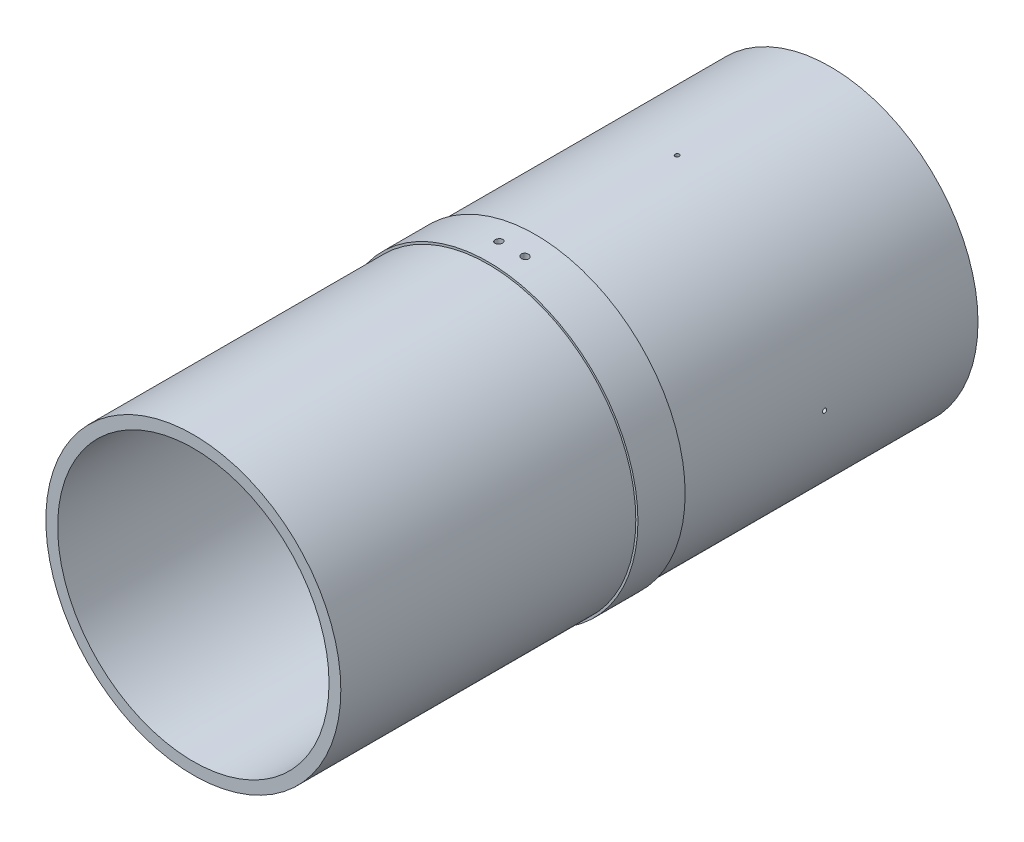
SolidWorks part; units mm, degrees
ref_plane "Front Plane" through (0, 0, 0) normal (0, 0, 1) x (1, 0, 0)
ref_plane "Top Plane" through (0, 0, 0) normal (0, 1, 0) x (1, 0, 0)
ref_plane "Right Plane" through (0, 0, 0) normal (1, 0, 0) x (0, 0, -1)
sketch "Sketch1" plane through (0, 0, 0) normal (0, 0, 1) x (1, 0, 0)
  circle A0 centre (0, 0) radius 79.375
  circle A1 centre (0, 0) radius 73.025
  dimension "D1" = 158.75
  dimension "D2" = 6.35
extrude "Boss-Extrude1" add sketch "Sketch1" along normal blind 342.9
ref_plane "Plane1" through (0, 0, 171.45) normal (0, 0, 1) x (1, 0, 0)
sketch "Sketch2" plane through (0, 0, 171.45) normal (0, 0, 1) x (1, 0, 0)
  circle A0 centre (0, 0) radius 79.375 construction
  circle A1 centre (0, 0) radius 79.375
  circle A2 centre (0, 0) radius 80.518
extrude "Boss-Extrude2" add sketch "Sketch2" against normal mid plane 25.4
sketch "Sketch5" plane through (0, 0, 171.45) normal (0, 0, 1) x (1, 0, 0)
  line L0 (0, 0) -> (0, 47.1719) construction
  line L1 (0, 0) -> (7.0176, 80.2116) construction
  circle A1 centre (0, 0) radius 80.518 construction
  point P2 (0, 0)
  point P5 (8.3839, 95.8285)
  point P7 (0, 0)
  point P8 (0, 0)
  dimension "D1" = 5
ref_plane "Plane2" through (7.0176, 80.2116, 0) normal (0.0872, 0.9962, 0) x (0, 0, 1)
hole_wizard "5/32 (0.15625) Diameter Hole1" positions "Sketch9" profile "Sketch10" hole size "5/32" standard "ANSI Inch" end condition up to next
sketch "Sketch9" plane through (7.0176, 80.2116, 0) normal (0.0872, 0.9962, 0) x (0, 0, 1)
  point P0 (171.45, 0)
sketch "Sketch10" plane through (7.0176, 80.2116, 171.45) normal (0, 0, 1) x (-0.9962, 0.0872, 0)
  line L0 (0, 0) -> (0, 7.493)
  line L1 (0, 7.493) -> (1.9844, 7.493)
  line L2 (1.9844, 7.493) -> (1.9844, 0)
  line L5 (1.9844, 0) -> (0, 0)
  line L11 (0, -6.35) -> (0, 107.95) construction
  dimension "Thru Hole Dia." = 3.9688
  dimension "Thru Hole Depth" = 7.493
mirror "Mirror1" about plane through (0, 0, 0) normal (1, 0, 0) of "5/32 (0.15625) Diameter Hole1"
ref_plane "Plane3" through (0, 79.375, 0) normal (0, 1, 0) x (1, 0, 0)
sketch "Sketch11" plane through (0, 79.375, 0) normal (0, 1, 0) x (1, 0, 0)
  line L0 (80.518, -158.75) -> (-80.518, -158.75) construction
  point P0 (0, -82.55)
  dimension "D1" = 76.2
hole_wizard "#4-40 Tapped Hole1" positions "Sketch12" profile "Sketch13" tap size "#4-40" standard "ANSI Inch" end condition up to next
sketch "Sketch12" plane through (0, 79.375, 0) normal (0, 1, 0) x (1, 0, 0)
  point P0 (0, -82.55)
sketch "Sketch13" plane through (0, 79.375, 82.55) normal (1, 0, 0) x (0, 0, 1)
  line L0 (0, 0) -> (0, 6.35)
  line L1 (0, 6.35) -> (1.1303, 6.35)
  line L2 (1.1303, 6.35) -> (1.1303, 0)
  line L5 (1.1303, 0) -> (0, 0)
  line L11 (0, -6.35) -> (0, 107.95) construction
  dimension "Thru Tap Drill Dia." = 2.2606
  dimension "Thru Tap Drill Depth" = 6.35
cosmetic thread "Hole Thread1" parameters "D2"=2.8448
pattern_circular "CirPattern1" count 4 over 360 about axis through (0, 0, 0) along (0, 0, 1) of "#4-40 Tapped Hole1"
cosmetic thread "Hole Thread2" parameters "D2"=2.8448
cosmetic thread "Hole Thread3" parameters "D2"=2.8448
cosmetic thread "Hole Thread4" parameters "D2"=2.8448
